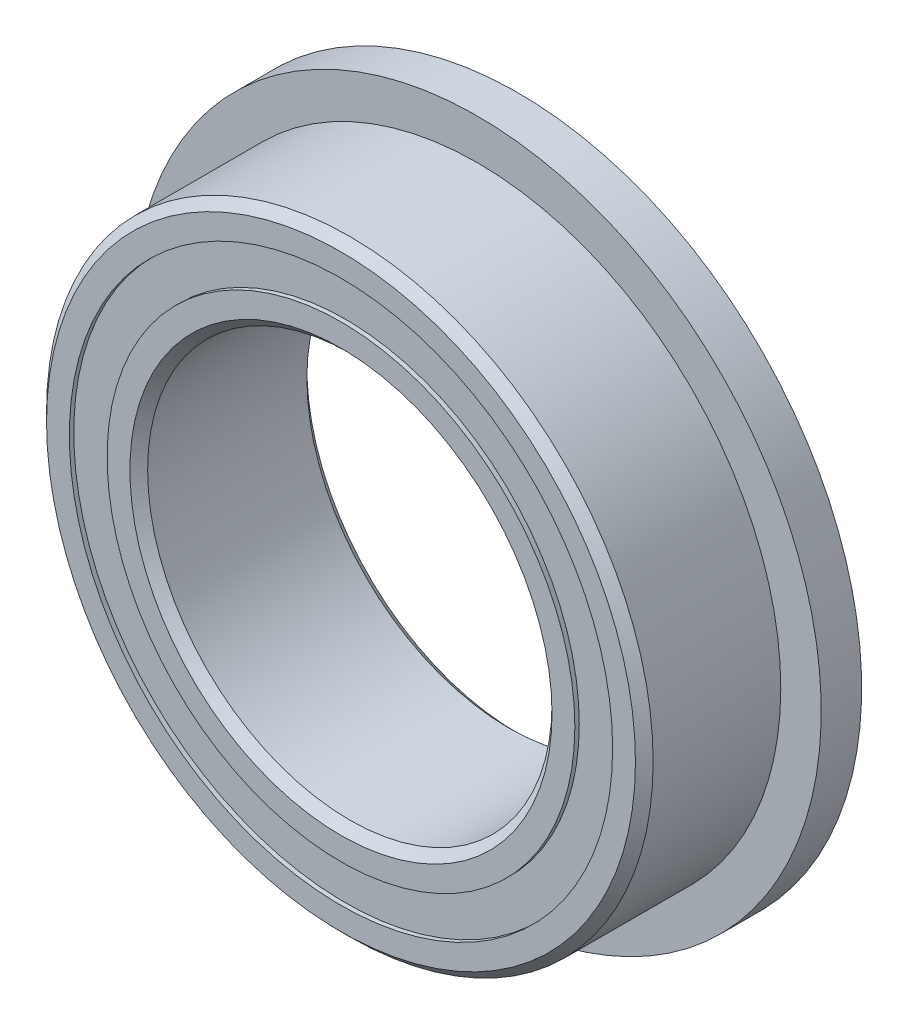
SolidWorks part; units mm, degrees
material "AISI 1020"
ref_plane "Front Plane" through (0, 0, 0) normal (0, 0, 1) x (1, 0, 0)
ref_plane "Top Plane" through (0, 0, 0) normal (0, 1, 0) x (1, 0, 0)
ref_plane "Right Plane" through (0, 0, 0) normal (1, 0, 0) x (0, 0, -1)
sketch "Sketch1" plane through (0, 0, 0) normal (1, 0, 0) x (0, 0, -1)
  line L0 (-1.75, 0) -> (1.75, 0) construction
  line L1 (0, 6) -> (0, -6) construction
  line L2 (1.575, 6) -> (-1.575, 6)
  line L3 (-1.575, 6) -> (-1.75, 5.825)
  line L4 (-1.75, 5.825) -> (-1.75, 5.3736)
  line L5 (-1.75, 5.3736) -> (-0.7778, 5.3736)
  line L6 (1.75, 5.3736) -> (0.7778, 5.3736)
  line L7 (1.75, 5.825) -> (1.75, 5.3736)
  line L8 (1.575, 6) -> (1.75, 5.825)
  line L9 (0, 6) -> (0, 5) construction
  line L10 (0, 5) -> (0, 4) construction
  arc A0 (-0.7778, 5.3736) -> (0.7778, 5.3736) centre (0, 5) cw
  point P14 (0, 4)
  dimension "D3" = 1.5556
  dimension "D1" = 45
  dimension "Width" = 3.5
  dimension "OD" = 12
  dimension "D2" = 0.175
  dimension "Shaft Dia" = 8
  dimension "D4" = 0.3736
revolve "Revolve1" add sketch "Sketch1" angle 360 about L0
sketch "Sketch3" plane through (0, 0, 0) normal (1, 0, 0) x (0, 0, -1)
  line L0 (-1.75, 4.6264) -> (-0.7778, 4.6264)
  line L1 (0, 6) -> (0, -6) construction
  line L2 (-1.75, 5.825) -> (-1.75, 5.3736) construction
  line L3 (-1.75, 4.6264) -> (-1.75, 4.175)
  line L4 (-1.575, 6) -> (-1.75, 5.825) construction
  line L5 (-1.75, 4.175) -> (-1.575, 4)
  line L6 (-1.575, 4) -> (1.575, 4)
  line L7 (1.575, 6) -> (1.575, -6) construction
  line L8 (1.575, 4) -> (1.75, 4.175)
  line L9 (1.75, -5.825) -> (1.75, 5.825) construction
  line L10 (1.75, 4.175) -> (1.75, 4.6264)
  line L11 (1.75, 4.6264) -> (0.7778, 4.6264)
  line L13 (1.575, 6) -> (1.75, 5.825) construction
  arc A0 (0.7778, 5.3736) -> (-0.7778, 5.3736) centre (0, 5) ccw construction
  arc A1 (0.7778, 4.6264) -> (-0.7778, 4.6264) centre (0, 5) cw
revolve "Revolve3" add sketch "Sketch3" angle 360 about L0
sketch "Sketch4" plane through (0, 0, 0) normal (1, 0, 0) x (0, 0, -1)
  line L0 (-0.8629, 5) -> (0.8629, 5)
  arc A2 (-0.8629, 5) -> (0.8629, 5) centre (0, 5) cw
  arc A3 (0.7778, 5.3736) -> (-0.7778, 5.3736) centre (0, 5) ccw construction
revolve "Revolve4" add sketch "Sketch4" angle 360 about L0
ref_axis "Axis1" through (0, 0, -1.75) along (0, 0, 1)
pattern_circular "CirPattern1" count 12 every 30 about axis through (0, 0, -1.75) along (0, 0, 1) of bodies 104
sketch "Sketch5" plane through (0, 0, 0) normal (1, 0, 0) x (0, 0, -1)
  line L0 (-1.75, 5.3736) -> (-0.7778, 5.3736) construction
  line L1 (-1.6625, 5.3736) -> (-0.8629, 5.3736)
  line L2 (-1.6625, 5.3736) -> (-1.6625, 4.6264)
  line L3 (-1.6625, 4.6264) -> (-0.8629, 4.6264)
  line L4 (-0.8629, 5.3736) -> (-0.8629, 4.6264)
  line L5 (-1.75, 4.6264) -> (-0.7778, 4.6264) construction
  line L6 (1.75, 5.3736) -> (0.7778, 5.3736) construction
  line L7 (1.6625, 5.3736) -> (0.8629, 5.3736)
  line L8 (1.6625, 5.3736) -> (1.6625, 4.6264)
  line L9 (1.6625, 4.6264) -> (0.8629, 4.6264)
  line L10 (0.8629, 5.3736) -> (0.8629, 4.6264)
  line L11 (1.75, 4.6264) -> (0.7778, 4.6264) construction
  line L12 (-1.575, 6) -> (-1.75, 5.825) construction
  point P18 (-1.6625, 5.9125)
revolve "Revolve5" add sketch "Sketch5" angle 360 about L0
sketch "Sketch6" plane through (0, 0, 0) normal (1, 0, 0) x (0, 0, -1)
  line L0 (1.75, 0) -> (-1.75, 0) construction
  line L1 (1.75, 5.3736) -> (0.95, 5.3736)
  line L2 (1.75, 5.3736) -> (1.75, 6.8)
  line L3 (1.75, 6.8) -> (0.95, 6.8)
  line L4 (0.95, 5.3736) -> (0.95, 6.8)
  dimension "Th" = 0.8
  dimension "Flange OD" = 13.6
revolve "Revolve6" add sketch "Sketch6" angle 360 about L0
equation "\"D2@Sketch1\" = \"Width@Sketch1\"*.05"
equation "\"D3@Sketch1\" = \"Width@Sketch1\"/2.25"
equation "\"D4@Sketch1\" = (((\"OD@Sketch1\"-\"Width@Sketch1\")/2)/3.25)/3.5"
equation "\"D2@CirPattern1\" = 360/\"Balls@CirPattern1\""
